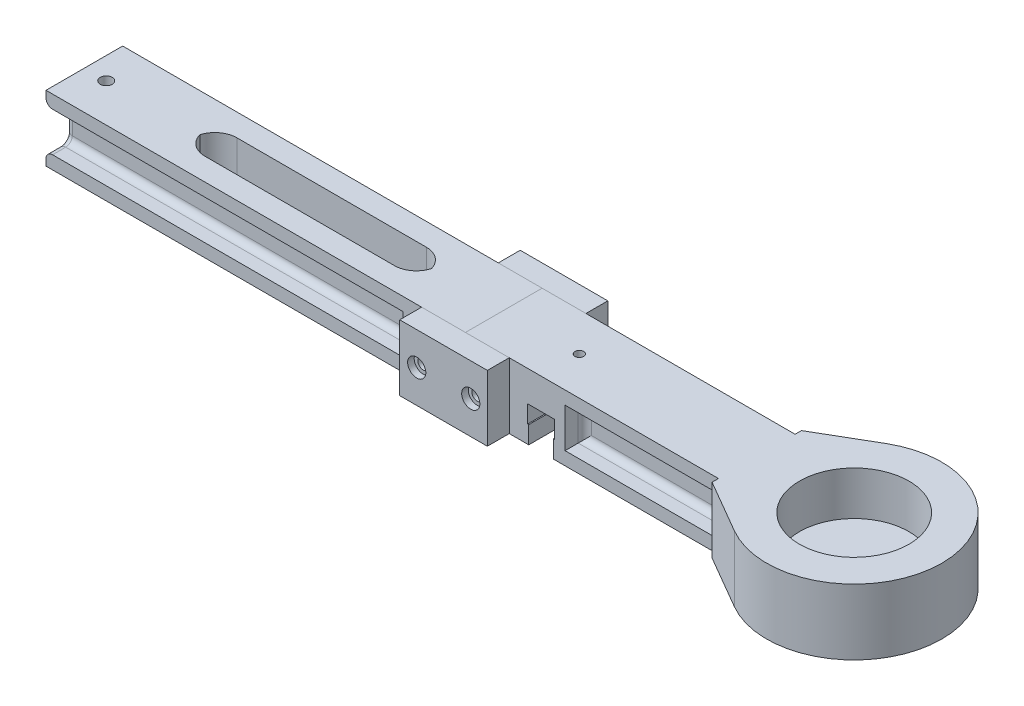
SolidWorks part; units mm, degrees
material "PLA "
ref_plane "Front Plane" through (0, 0, 0) normal (0, 0, 1) x (1, 0, 0)
ref_plane "Top Plane" through (0, 0, 0) normal (0, 1, 0) x (1, 0, 0)
ref_plane "Right Plane" through (0, 0, 0) normal (1, 0, 0) x (0, 0, -1)
sketch "Sketch1" plane through (0, 0, 0) normal (0, 1, 0) x (1, 0, 0)
  line L0 (0, 0) -> (-247, 0) construction
  line L1 (-247, 0) -> (-447, 0) construction
  dimension "D1" = 247
  dimension "D2" = 200
sketch "Sketch2" plane through (0, 0, 0) normal (0, 1, 0) x (1, 0, 0)
  line L1 (-247, -17.5) -> (0, -17.5)
  line L2 (-247, -17.5) -> (-247, 17.5)
  line L3 (-247, 17.5) -> (0, 17.5)
  line L4 (0, -17.5) -> (0, 17.5)
  point P4 (-247, 0)
  dimension "D1" = 35
extrude "Boss-Extrude1" add sketch "Sketch2" along normal blind 30 contours L1 L4 L3 L2
sketch "Sketch3" plane through (0, 0, 0) normal (0, -1, 0) x (1, 0, 0)
  line L0 (0, 0) -> (-21, 0) construction
  line L1 (0, 0) -> (-247, 0) construction
  circle A0 centre (-21, 0) radius 5.6
  dimension "D2" = 11.2
  dimension "D1" = 21
extrude "Cut-Extrude1" cut sketch "Sketch3" against normal through all
sketch "Sketch4" plane through (0, 30, 0) normal (0, 1, 0) x (1, 0, 0)
  line L0 (0, -17.5) -> (0, 17.5) construction
  line L1 (-14.9, 3.5218) -> (-21, 7.0437)
  line L2 (-21, 7.0437) -> (-27.1, 3.5218)
  line L3 (-27.1, 3.5218) -> (-27.1, -3.5218)
  line L4 (-27.1, -3.5218) -> (-21, -7.0437)
  line L5 (-21, -7.0437) -> (-14.9, -3.5218)
  line L6 (-14.9, -3.5218) -> (-14.9, 3.5218)
  line L7 (-27.1, 0) -> (-14.9, 0)
  circle A0 centre (-21, 0) radius 6.1 construction
  dimension "D1" = 12.2
extrude "Cut-Extrude2" cut sketch "Sketch4" against normal blind 22 contours L1 L2 L3 L4 L5 L6
sketch "Sketch5" plane through (0, 0, 0) normal (1, 0, 0) x (0, 0, -1)
  line L0 (0, 8) -> (0, 1) construction
  line L1 (-3.5218, 8) -> (3.5218, 8) construction
  line L2 (0, 1) -> (0, -2.0977) construction
  line L3 (2.5, 1) -> (2.5, -2.0977)
  line L4 (-2.5, 1) -> (-2.5, -2.0977)
  arc A0 (2.5, 1) -> (-2.5, 1) centre (0, 1) ccw
  arc A1 (-2.5, -2.0977) -> (2.5, -2.0977) centre (0, -2.0977) ccw
  point P5 (0, -0.5488)
  dimension "D1" = 7
  dimension "D2" = 5
sketch "Sketch6" plane through (0, 0, 0) normal (1, 0, 0) x (0, 0, -1)
  line L0 (0, 8) -> (0, 16) construction
  line L1 (-3.5218, 8) -> (3.5218, 8) construction
  line L2 (-17.5, 30) -> (17.5, 30) construction
  line L3 (-11.0435, 16) -> (11.453, 16)
  line L4 (-11.0435, 16) -> (-11.0435, 30)
  line L5 (-11.0435, 30) -> (11.453, 30)
  line L6 (11.453, 16) -> (11.453, 30)
  dimension "D1" = 8
extrude "Boss-Extrude3" add sketch "Sketch6" against normal blind 38
sketch "Sketch7" plane through (0, 0, 17.5) normal (0, 0, 1) x (1, 0, 0)
  line L0 (-21, 16) -> (-14.9, 16) construction
  line L1 (-27.1, 16) -> (-21, 16) construction
  line L2 (-27.1, 8) -> (-27.1, 16) construction
  line L3 (-14.9, 8) -> (-14.9, 16) construction
  line L4 (-15.4, 0) -> (-15.4, 8) construction
  line L5 (-26.6, 8) -> (-26.6, 0) construction
  line L6 (-21, 16) -> (-14.9, 16)
  line L7 (-27.1, 16) -> (-21, 16)
  line L8 (-27.1, 8) -> (-27.1, 16)
  line L9 (-14.9, 8) -> (-14.9, 16)
  line L10 (-15.4, 0) -> (-15.4, 8)
  line L11 (-26.6, 8) -> (-26.6, 0)
  line L12 (-27.1, 8) -> (-26.6, 8)
  line L13 (-15.4, 8) -> (-14.9, 8)
  line L14 (-26.6, 0) -> (-15.4, 0)
extrude "Cut-Extrude4" cut sketch "Sketch7" against normal up to vertex (17.5 mm away) up to point (-14.9, 30, 0)
sketch "Sketch9" plane through (0, 30, 0) normal (0, 1, 0) x (1, 0, 0)
  line L0 (-27.1, 3.5218) -> (-14.9, -3.5218) construction
  line L1 (-27.1, -3.5218) -> (-14.9, 3.5218) construction
  line L6 (-14.9, 3.5218) -> (-21, 7.0437)
  line L7 (-21, 7.0437) -> (-27.1, 3.5218)
  line L8 (-27.1, 3.5218) -> (-27.1, -3.5218)
  line L9 (-27.1, -3.5218) -> (-21, -7.0437)
  line L10 (-21, -7.0437) -> (-14.9, -3.5218)
  line L11 (-14.9, -3.5218) -> (-14.9, 3.5218)
  line L12 (-14.9, 3.5218) -> (-21, 7.0437) construction
  line L13 (-21, 7.0437) -> (-27.1, 3.5218) construction
  line L14 (-27.1, 3.5218) -> (-27.1, -3.5218) construction
  line L15 (-27.1, -3.5218) -> (-21, -7.0437) construction
  line L16 (-21, -7.0437) -> (-14.9, -3.5218) construction
  line L17 (-14.9, -3.5218) -> (-14.9, 3.5218) construction
  circle A0 centre (-21, 0) radius 2
  dimension "D2" = 4
  dimension "D1" = 0
extrude "Cut-Extrude5" cut sketch "Sketch9" against normal blind 38
sketch "Sketch15" plane through (0, 30, 0) normal (0, 1, 0) x (1, 0, 0)
  line L0 (-247, 0) -> (-237, 0) construction
  line L1 (0, 0) -> (-247, 0) construction
  circle A0 centre (-237, 0) radius 2.75
  dimension "D2" = 5.5
  dimension "D1" = 10
extrude "Cut-Extrude10" cut sketch "Sketch15" against normal blind 9
sketch "Sketch16" plane through (0, 0, 0) normal (0, -1, 0) x (1, 0, 0)
  line L1 (-241.1302, 2.6504) -> (-241.3604, -2.2517)
  line L2 (-241.3604, -2.2517) -> (-237.2302, -4.9021)
  line L3 (-237.2302, -4.9021) -> (-232.8698, -2.6504)
  line L4 (-232.8698, -2.6504) -> (-232.6396, 2.2517)
  line L5 (-232.6396, 2.2517) -> (-236.7698, 4.9021)
  line L6 (-236.7698, 4.9021) -> (-241.1302, 2.6504)
  circle A0 centre (-237, 0) radius 2.75 construction
  circle A1 centre (-237, 0) radius 2.75 construction
  circle A2 centre (-237, 0) radius 4.25 construction
  dimension "D1" = 8.5
extrude "Cut-Extrude11" cut sketch "Sketch16" against normal up to surface (21 mm away) up to face at (-237, 21, 2.75)
sketch "Sketch17" plane through (0, 30, 0) normal (0, 1, 0) x (1, 0, 0)
  line L0 (0, 0) -> (-247, 0) construction
  line L2 (-58.6673, -9.5384) -> (-188.3327, -9.5384)
  line L3 (-58.6673, -9.5384) -> (-58.6673, 9.5384)
  line L4 (-58.6673, 9.5384) -> (-188.3327, 9.5384)
  line L5 (-188.3327, -9.5384) -> (-188.3327, 9.5384)
  line L6 (-58.6673, -9.5384) -> (-188.3327, 9.5384) construction
  line L7 (-58.6673, 9.5384) -> (-188.3327, -9.5384) construction
  point P4 (-123.5, 0)
extrude "Cut-Extrude12" [suppressed] cut sketch "Sketch17" against normal through all
fillet "Fillet1" [suppressed] radius 10
sketch "Sketch19" plane through (0, 0, 0) normal (1, 0, 0) x (0, 0, -1)
  line L5 (17.5, 0) -> (17.5, 30)
  line L6 (17.5, 30) -> (-17.5, 30)
  line L7 (-17.5, 30) -> (-17.5, 0)
  line L8 (-17.5, 0) -> (17.5, 0)
  line L9 (17.5, 0) -> (17.5, 30)
  line L10 (17.5, 30) -> (-17.5, 30)
  line L11 (-17.5, 30) -> (-17.5, 0)
  line L12 (-17.5, 0) -> (17.5, 0)
  dimension "D1" = 0
extrude "Boss-Extrude5" add sketch "Sketch19" along normal blind 55
sketch "Sketch18" plane through (0, 30, 0) normal (0, 1, 0) x (1, 0, 0)
  line L0 (84.4055, -34.5857) -> (84.4055, 34.5857) construction
  line L1 (55, 17.5) -> (55, -17.5)
  line L2 (55, -17.5) -> (84.4055, -34.5857)
  line L5 (84.4055, 34.5857) -> (55, 17.5)
  line L6 (55, 0) -> (84.4055, 0) construction
  arc A1 (84.4055, -34.5857) -> (84.4055, 34.5857) centre (104.5011, 0) ccw
  point P7 (144.5011, 0)
  dimension "D1" = 40
extrude "Boss-Extrude4" add sketch "Sketch18" against normal up to vertex (30 mm away) up to point (55, 0, 17.5)
sketch "Sketch20" plane through (0, 0, 0) normal (0, -1, 0) x (1, 0, 0)
  circle A0 centre (104.5011, 0) radius 25
  dimension "D1" = 50
sketch "Sketch21" plane through (0, 30, 0) normal (0, 1, 0) x (1, 0, 0)
  circle A1 centre (104.5011, 0) radius 25
  circle A2 centre (104.5011, 0) radius 25
  dimension "D1" = 0
extrude "Cut-Extrude14" cut sketch "Sketch21" against normal blind 20
sketch "Sketch22" plane through (0, 0, 0) normal (0, -1, 0) x (1, 0, 0)
  line L0 (-247, 0) -> (144.5011, 0) construction
  arc A0 (84.4055, -34.5857) -> (84.4055, 34.5857) centre (104.5011, 0) ccw construction
  point P6 (-21, 0)
sketch "Sketch23" plane through (0, 0, 17.5) normal (0, 0, 1) x (1, 0, 0)
  line L0 (-55.4989, 91.556) -> (-55.4989, -31.556)
  line L3 (144.5011, 0) -> (144.5011, 64.4466) construction
  line L4 (-27.1, 16) -> (-27.1, 55.3644) construction
  point P3 (-55.4989, 30)
  dimension "D1" = 200
split "Split1" trim tools "Sketch23" bodies to split 118 resulting bodies 119 120
sketch "Sketch24" plane through (0, 0, 17.5) normal (0, 0, 1) x (1, 0, 0)
  line L0 (-55.4989, 30) -> (-55.4989, 0) construction
  line L1 (0, 0) -> (-247, 0) construction
  line L2 (-55.4989, 91.556) -> (-55.4989, -31.556) construction
  line L3 (-55.4989, 0) -> (-55.4989, 15) construction
  line L4 (-55.4989, 30) -> (55, 30) construction
  line L5 (-75.4989, 0) -> (-35.4989, 0)
  line L6 (-75.4989, 0) -> (-75.4989, 30)
  line L7 (-75.4989, 30) -> (-35.4989, 30)
  line L8 (-35.4989, 0) -> (-35.4989, 30)
  line L9 (-75.4989, 0) -> (-35.4989, 30) construction
  line L10 (-75.4989, 30) -> (-35.4989, 0) construction
  dimension "D1" = 40
extrude "Boss-Extrude6" add sketch "Sketch24" along normal blind 10 separate body contours L6 L7 L8 L5
sketch "Sketch26" plane through (0, 0, -17.5) normal (0, 0, -1) x (-1, 0, 0)
  line L4 (35.4989, 0) -> (75.4989, 0)
  line L5 (35.4989, 30) -> (35.4989, 0)
  line L6 (75.4989, 30) -> (35.4989, 30)
  line L7 (75.4989, 0) -> (75.4989, 30)
  line L8 (35.4989, 0) -> (75.4989, 0)
  line L9 (35.4989, 30) -> (35.4989, 0)
  line L10 (75.4989, 30) -> (35.4989, 30)
  line L11 (75.4989, 0) -> (75.4989, 30)
  dimension "D1" = 0
extrude "Boss-Extrude7" add sketch "Sketch26" along normal blind 10 separate body
sketch "Sketch27" plane through (0, 0, -27.5) normal (0, 0, -1) x (-1, 0, 0)
  line L0 (35.4989, 15) -> (75.4989, 15) construction
  line L1 (35.4989, 30) -> (35.4989, 0) construction
  line L2 (75.4989, 0) -> (75.4989, 30) construction
  circle A0 centre (43.074, 15) radius 2.5
  circle A1 centre (67.7461, 15) radius 2.5
  dimension "D1" = 5
extrude "Cut-Extrude15" cut sketch "Sketch27" against normal through all
sketch "Sketch31" plane through (0, 0, -27.5) normal (0, 0, -1) x (-1, 0, 0)
  line L1 (45.4412, 10.9) -> (47.8083, 15)
  line L2 (47.8083, 15) -> (45.4412, 19.1)
  line L3 (45.4412, 19.1) -> (40.7069, 19.1)
  line L4 (40.7069, 19.1) -> (38.3397, 15)
  line L5 (38.3397, 15) -> (40.7069, 10.9)
  line L6 (40.7069, 10.9) -> (45.4412, 10.9)
  line L7 (70.1133, 10.9) -> (72.4804, 15)
  line L8 (72.4804, 15) -> (70.1133, 19.1)
  line L9 (70.1133, 19.1) -> (65.379, 19.1)
  line L10 (65.379, 19.1) -> (63.0119, 15)
  line L11 (63.0119, 15) -> (65.379, 10.9)
  line L12 (65.379, 10.9) -> (70.1133, 10.9)
  circle A0 centre (43.074, 15) radius 4.1 construction
  circle A1 centre (67.7461, 15) radius 4.1 construction
  dimension "D1" = 8.2
extrude "Cut-Extrude17" cut sketch "Sketch31" against normal blind 3
sketch "Sketch32" plane through (0, 0, 27.5) normal (0, 0, 1) x (1, 0, 0)
  circle A0 centre (-67.7461, 15) radius 4.15
  circle A1 centre (-43.074, 15) radius 4.15
  dimension "D1" = 8.3
extrude "Cut-Extrude18" cut sketch "Sketch32" against normal blind 3
sketch "Sketch28" plane through (-247, 0, 0) normal (-1, 0, 0) x (0, 0, 1)
  line L1 (-17.5, 30) -> (17.5, 30)
  line L2 (-17.5, 30) -> (-17.5, 36.9638)
  line L3 (-17.5, 36.9638) -> (17.5, 36.9638)
  line L4 (17.5, 30) -> (17.5, 36.9638)
extrude "Boss-Extrude8" [suppressed] add sketch "Sketch28" against normal blind 40
sketch "Sketch30" plane through (0, 21, 0) normal (0, -1, 0) x (1, 0, 0)
  circle A0 centre (-237, 0) radius 2.75 construction
  circle A1 centre (-237, 0) radius 2.75
sketch "Sketch33" plane through (-247, 0, 0) normal (-1, 0, 0) x (0, 0, 1)
  line L0 (-17.5, 30) -> (-17.5, 24)
  line L1 (-17.5, 30) -> (-17.5, 0) construction
  line L2 (-17.5, 24) -> (17.5, 24) construction
  line L3 (17.5, 30) -> (17.5, 0) construction
  line L4 (-17.5, 6) -> (17.5, 6) construction
  line L5 (0, 24) -> (0, 6) construction
  line L6 (17.5, 0) -> (17.5, 30) construction
  line L7 (17.5, 0) -> (-17.5, 0) construction
  line L8 (17.5, 30) -> (-17.5, 30) construction
  line L9 (-8.5, 24) -> (-8.5, 6)
  line L10 (8.5, 24) -> (8.5, 6)
  line L11 (-8.5, 15) -> (8.5, 15) construction
  line L12 (-17.5, 24) -> (-8.5, 24)
  line L13 (-8.5, 6) -> (-17.5, 6)
  line L14 (-17.5, 6) -> (-17.5, 0)
  line L15 (-17.5, 0) -> (-17.5, 30) construction
  line L16 (-17.5, 0) -> (17.5, 0)
  line L17 (27.5, 0) -> (17.5, 0) construction
  line L18 (17.5, 0) -> (17.5, 6)
  line L19 (17.5, 6) -> (8.5, 6)
  line L20 (8.5, 24) -> (17.5, 24)
  line L21 (17.5, 24) -> (17.5, 30)
  line L22 (17.5, 30) -> (-17.5, 30)
  line L24 (-24.3906, 37.0172) -> (24.3906, 37.0172)
  line L25 (-24.3906, 37.0172) -> (-24.3906, -7.0172)
  line L26 (-24.3906, -7.0172) -> (24.3906, -7.0172)
  line L27 (24.3906, 37.0172) -> (24.3906, -7.0172)
  line L28 (-24.3906, 37.0172) -> (24.3906, -7.0172) construction
  line L29 (-24.3906, -7.0172) -> (24.3906, 37.0172) construction
  point P9 (0, 24)
  point P12 (0, 6)
  point P24 (0, 15)
  point P25 (0, 15)
  dimension "D1" = 6
  dimension "D2" = 6
  dimension "D3" = 17
extrude "Cut-Extrude19" cut sketch "Sketch33" against normal blind 163 contours L24 L27 L26 L25
sketch "Sketch34" plane through (0, 0, 0) normal (1, 0, 0) x (0, 0, -1)
  line L4 (24.3906, 37.0172) -> (-24.3906, 37.0172)
  line L5 (-24.3906, 37.0172) -> (-24.3906, -7.0172)
  line L6 (-24.3906, -7.0172) -> (24.3906, -7.0172)
  line L7 (24.3906, -7.0172) -> (24.3906, 37.0172)
  line L8 (24.3906, 37.0172) -> (-24.3906, 37.0172)
  line L9 (-24.3906, 37.0172) -> (-24.3906, -7.0172)
  line L10 (-24.3906, -7.0172) -> (24.3906, -7.0172)
  line L11 (24.3906, -7.0172) -> (24.3906, 37.0172)
  line L20 (-17.5, 30) -> (-17.5, 24)
  line L21 (-17.5, 24) -> (-8.5, 24)
  line L22 (-8.5, 24) -> (-8.5, 6)
  line L23 (-8.5, 6) -> (-17.5, 6)
  line L24 (-17.5, 6) -> (-17.5, 0)
  line L25 (-17.5, 0) -> (17.5, 0)
  line L26 (17.5, 0) -> (17.5, 6)
  line L27 (17.5, 6) -> (8.5, 6)
  line L28 (8.5, 6) -> (8.5, 24)
  line L29 (8.5, 24) -> (17.5, 24)
  line L30 (17.5, 24) -> (17.5, 30)
  line L31 (17.5, 30) -> (-17.5, 30)
  line L32 (-17.5, 30) -> (-17.5, 24)
  line L33 (-17.5, 24) -> (-8.5, 24)
  line L34 (-8.5, 24) -> (-8.5, 6)
  line L35 (-8.5, 6) -> (-17.5, 6)
  line L36 (-17.5, 6) -> (-17.5, 0)
  line L37 (-17.5, 0) -> (17.5, 0)
  line L38 (17.5, 0) -> (17.5, 6)
  line L39 (17.5, 6) -> (8.5, 6)
  line L40 (8.5, 6) -> (8.5, 24)
  line L41 (8.5, 24) -> (17.5, 24)
  line L42 (17.5, 24) -> (17.5, 30)
  line L43 (17.5, 30) -> (-17.5, 30)
  dimension "D1" = 0
  dimension "D2" = 0
extrude "Cut-Extrude20" cut sketch "Sketch34" against normal blind 10 and the other way blind 60
fillet "Fillet3" radius 3 12 edges at (-247, 24, 13) (-247, 6, 13) (-247, 6, -13) (-247, 24, -13) (-165.5, 24, 8.5) (-84, 15, 8.5) (-165.5, 6, 8.5) (-247, 15, 8.5) (-165.5, 6, -8.5) (-84, 15, -8.5) (-165.5, 24, -8.5) (-247, 15, -8.5)
fillet "Fillet4" radius 3 8 edges at (-10, 15, 8.5) (25, 24, 8.5) (60, 15, 8.5) (25, 6, 8.5) (-10, 15, -8.5) (25, 6, -8.5) (60, 15, -8.5) (25, 24, -8.5)
other "Save Bodies1"
sketch "Sketch29" plane through (0, 30, 0) normal (0, 1, 0) x (1, 0, 0)
  line L0 (-88.1262, 0) -> (-194.6695, 0) construction
  line L1 (0, 0) -> (-247, 0) construction
  line L2 (-88.1262, -7.2908) -> (-88.1262, 7.2908)
  line L3 (-88.1262, -7.2908) -> (-194.6695, -7.2908)
  line L4 (-194.6695, -7.2908) -> (-194.6695, 7.2908)
  line L5 (-194.6695, 7.2908) -> (-88.1262, 7.2908)
  point P7 (-88.1262, 0)
extrude "Cut-Extrude16" cut sketch "Sketch29" against normal through all
fillet "Fillet2" radius 10 4 edges at (-194.6695, 15, 7.2908) (-194.6695, 15, -7.2908) (-88.1262, 15, 7.2908) (-88.1262, 15, -7.2908)
other "Save Bodies2"
equation "\"2.5c\"=10"
